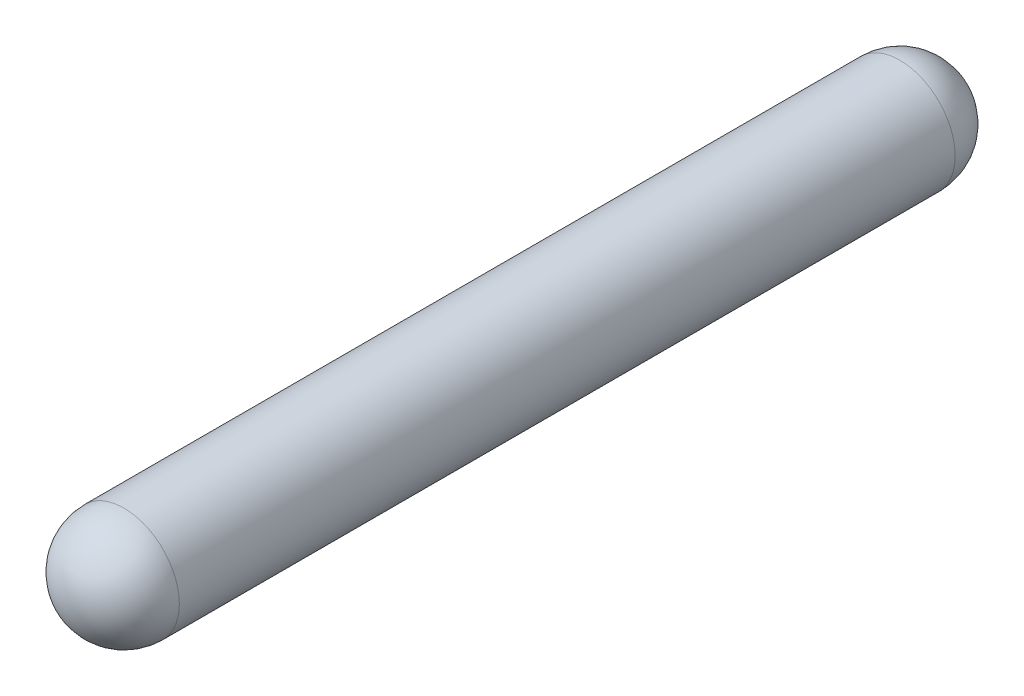
SolidWorks part; units mm, degrees
ref_plane "Front Plane" through (0, 0, 0) normal (0, 0, 1) x (1, 0, 0)
ref_plane "Top Plane" through (0, 0, 0) normal (0, 1, 0) x (1, 0, 0)
ref_plane "Right Plane" through (0, 0, 0) normal (1, 0, 0) x (0, 0, -1)
sketch "Sketch1" plane through (0, 0, 0) normal (0, 0, 1) x (1, 0, 0)
  circle A0 centre (0, 0) radius 5
  dimension "D1" = 10
extrude "Boss-Extrude1" add sketch "Sketch1" along normal blind 70.18
sketch "Sketch2" plane through (0, 0, 0) normal (1, 0, 0) x (0, 0, -1)
  line L0 (0, -5) -> (0, 5) construction
  line L1 (0, 5) -> (0, -5)
  arc A0 (0, 5) -> (0, -5) centre (0, 0) cw
  dimension "D1" = 5
revolve "Revolve1" add sketch "Sketch2" angle 360 about L1
sketch "Sketch3" plane through (0, 0, 0) normal (1, 0, 0) x (0, 0, -1)
  line L0 (-70.18, 5) -> (-70.18, -5)
  arc A0 (-70.18, 5) -> (-70.18, -5) centre (-70.18, 0) ccw
revolve "Revolve2" add sketch "Sketch3" angle 360 about L0
